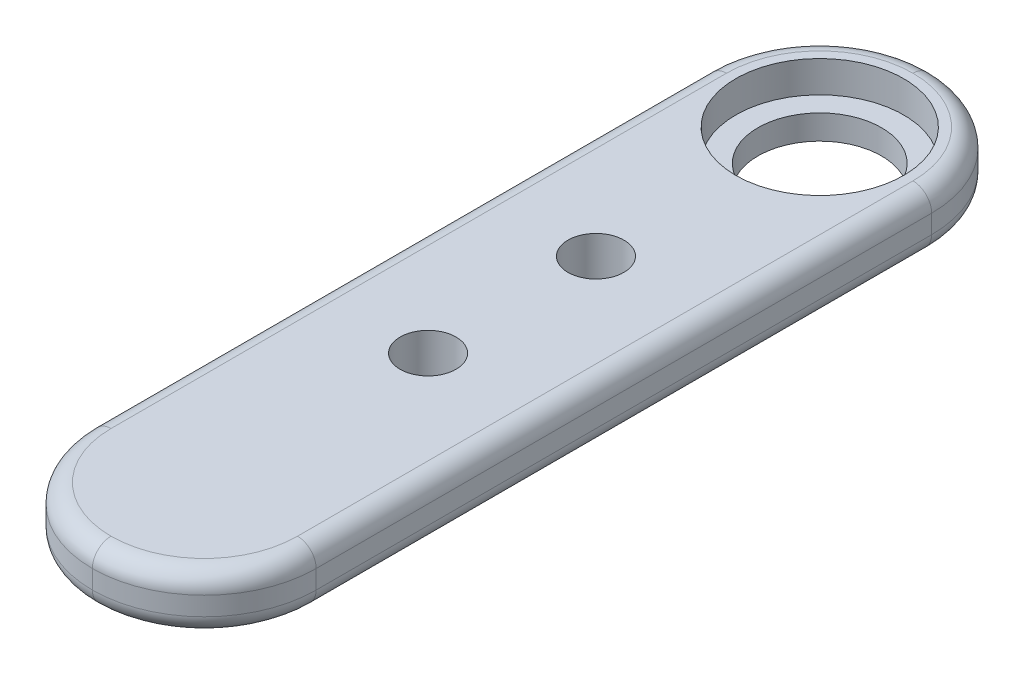
SolidWorks part; units mm, degrees
material "6061 Alloy"
ref_plane "Front Plane" through (0, 0, 0) normal (0, 0, 1) x (1, 0, 0)
ref_plane "Top Plane" through (0, 0, 0) normal (0, 1, 0) x (1, 0, 0)
ref_plane "Right Plane" through (0, 0, 0) normal (1, 0, 0) x (0, 0, -1)
sketch "Sketch1" plane through (0, 0, 0) normal (0, 1, 0) x (1, 0, 0)
  line L0 (0, 47.625) -> (0, -47.625) construction
  line L1 (-12.7, -47.625) -> (12.7, -47.625)
  line L2 (-12.7, -47.625) -> (-12.7, 47.625)
  line L3 (-12.7, 47.625) -> (12.7, 47.625)
  line L4 (12.7, -47.625) -> (12.7, 47.625)
  line L5 (-12.7, -47.625) -> (12.7, 47.625) construction
  line L6 (-12.7, 47.625) -> (12.7, -47.625) construction
  circle A1 centre (0, 9.525) radius 3.175
  circle A2 centre (0, -9.525) radius 3.175
  point P0 (0, 0)
  point P8 (0, 34.925)
  dimension "D3" = 25.4
  dimension "D2" = 12.7
  dimension "D6" = 6.35
  dimension "D1" = 25.4
  dimension "D4" = 19.05
  dimension "D5" = 38.1
extrude "Boss-Extrude1" add sketch "Sketch1" along normal blind 6.35
fillet "Fillet1" radius 12.7 4 edges at (-12.7, 3.175, -47.625) (12.7, 3.175, -47.625) (-12.7, 3.175, 47.625) (12.7, 3.175, 47.625)
fillet "Fillet2" radius 2.1167 12 edges at (8.9803, 0, 43.9053) (12.7, 0, 0) (8.9803, 0, -43.9053) (-8.9803, 0, -43.9053) (-12.7, 0, 0) (-8.9803, 6.35, -43.9053) (8.9803, 6.35, -43.9053) (12.7, 6.35, 0) (8.9803, 6.35, 43.9053) (-8.9803, 6.35, 43.9053) (-8.9803, 0, 43.9053) (-12.7, 6.35, 0)
ref_plane "Plane1" through (0, 0, 0) normal (-1, 0, 0) x (0, 0, 1)
sketch "Sketch3" plane through (0, 0, 0) normal (-1, 0, 0) x (0, 0, 1)
  line L0 (-34.925, 0) -> (-34.925, 6.35)
  line L1 (-44.45, 6.35) -> (-44.45, 2.7781)
  line L2 (-34.925, 6.35) -> (-45.5083, 6.35) construction
  line L3 (-44.45, 2.7781) -> (-34.925, 2.7781)
  line L5 (-41.9418, 2.7781) -> (-41.9418, 0)
  line L6 (47.625, 0) -> (-47.625, 0) construction
  line L7 (-41.9418, 0) -> (-34.925, 0) construction
  line L8 (-34.925, 6.35) -> (-44.45, 6.35) construction
  line L9 (-44.45, 6.35) -> (-44.45, 9.9219)
  line L10 (-44.45, 9.9219) -> (-34.925, 9.9219)
  line L11 (-34.925, 9.9219) -> (-34.925, 6.35)
  line L12 (-34.925, 9.9219) -> (-38.4593, -6.7056) construction
  line L13 (-33.2801, -5.4293) -> (-42.6715, -3.4331)
  line L14 (-42.6715, -3.4331) -> (-41.3513, 2.7781)
  line L15 (-34.925, 0) -> (-34.925, -5.0797)
  point P19 (-37.9758, -4.4312)
  dimension "D1" = 3.5719
  dimension "D2" = 12
  dimension "D3" = 9.6012
  dimension "D4" = 9.525
  dimension "D5" = 6.35
sketch "Sketch5" plane through (0, 6.35, 0) normal (0, 1, 0) x (1, 0, 0)
  circle A0 centre (0, 34.925) radius 9.525
  circle A1 centre (0, 34.925) radius 7.0168
extrude "Cut-Extrude2" cut sketch "Sketch5" against normal up to vertex (3.5719 mm away) up to point (0, 2.7781, -44.45)
extrude "Cut-Extrude3" cut sketch "Sketch5<2>" against normal up to vertex (6.35 mm away) contours A1 region at (0, 6.35, -34.925) up to point (0, 0, -41.9418)
sketch "Sketch5<2>" plane through (0, 6.35, 0) normal (0, 1, 0) x (1, 0, 0) same geometry as "Sketch5"
